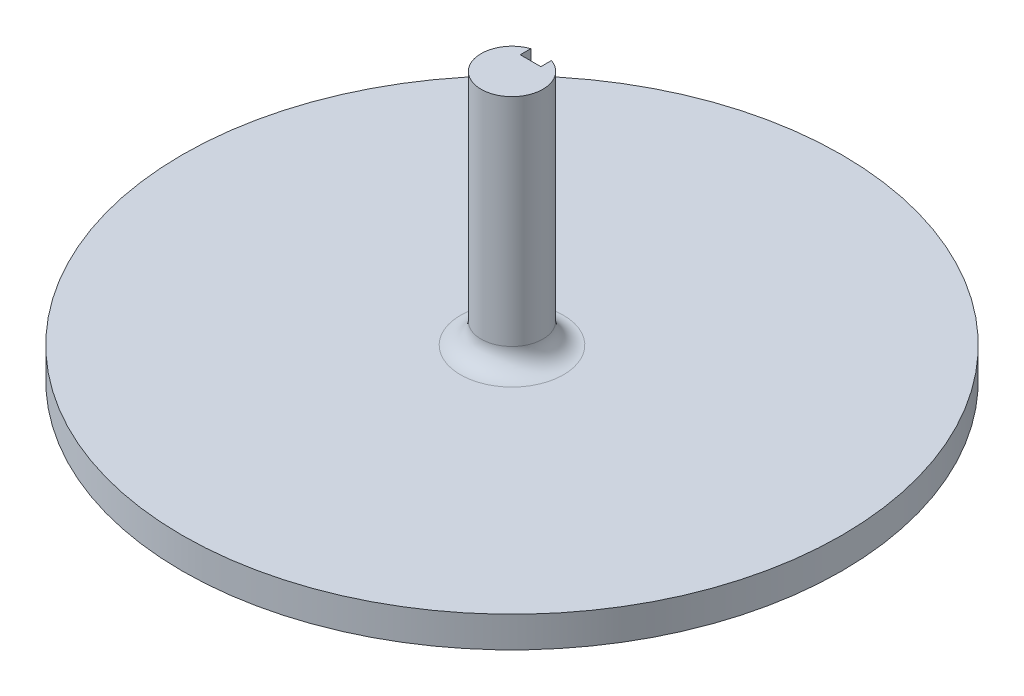
SolidWorks part; units mm, degrees
ref_plane "Front Plane" through (0, 0, 0) normal (0, 0, 1) x (1, 0, 0)
ref_plane "Top Plane" through (0, 0, 0) normal (0, 1, 0) x (1, 0, 0)
ref_plane "Right Plane" through (0, 0, 0) normal (1, 0, 0) x (0, 0, -1)
sketch "Sketch1" plane through (0, 0, 0) normal (0, 1, 0) x (1, 0, 0)
  line L0 (0, 3) -> (0, 1.8) construction
  line L1 (-1, 1.8) -> (1, 1.8)
  line L2 (1, 1.8) -> (1, 2.8284)
  line L3 (-1, 1.8) -> (-1, 2.8284)
  circle A0 centre (0, 0) radius 3
  point P8 (0, 1.8)
  dimension "D1" = 6
  dimension "D2" = 1.2
  dimension "D3" = 1
extrude "Boss-Extrude1" add sketch "Sketch1" along normal blind 20 contours L3 A0 L2 L1 region at (0, 0, 0.2088)
sketch "Sketch2" plane through (0, 0, 0) normal (0, -1, 0) x (1, 0, 0)
  circle A0 centre (0, 0) radius 3
extrude "Boss-Extrude2" add sketch "Sketch2" along normal blind 3
fillet "Fillet1" radius 1 2 edges at (-1, 0, -2.3142) (1, 0, -2.3142)
sketch "Sketch3" plane through (0, -3, 0) normal (0, -1, 0) x (1, 0, 0)
  circle A0 centre (0, 0) radius 32
  dimension "D1" = 64
extrude "Boss-Extrude3" add sketch "Sketch3" along normal blind 3
fillet "Fillet2" radius 2 1 edges at (0, -3, -3)
